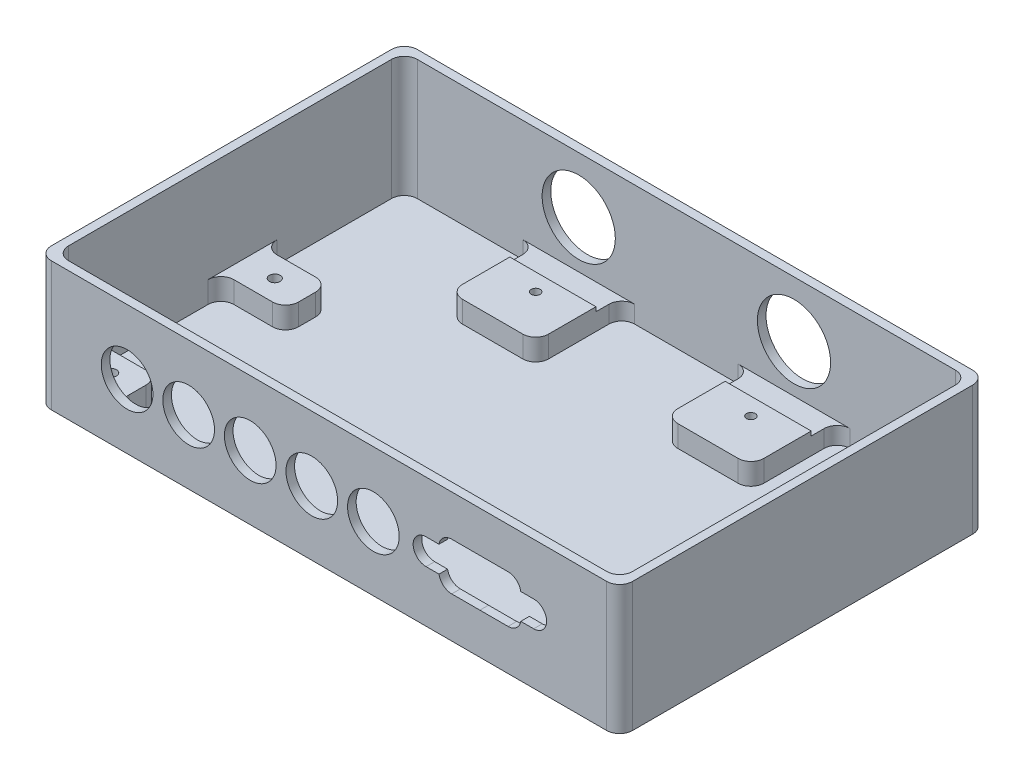
SolidWorks part; units mm, degrees
ref_plane "Ebene vorne" through (0, 0, 0) normal (0, 0, 1) x (1, 0, 0)
ref_plane "Ebene oben" through (0, 0, 0) normal (0, 1, 0) x (1, 0, 0)
ref_plane "Ebene rechts" through (0, 0, 0) normal (1, 0, 0) x (0, 0, -1)
sketch "Skizze1" plane through (0, 0, 0) normal (0, 1, 0) x (1, 0, 0)
  line L1 (0, 0) -> (135, 0)
  line L2 (0, 0) -> (0, 85)
  line L3 (0, 85) -> (135, 85)
  line L4 (135, 0) -> (135, 85)
  dimension "D1" = 85
  dimension "D2" = 135
extrude "Aufsatz-Linear austragen1" add sketch "Skizze1" along normal blind 30
shell "Schale1" thickness 2 removed face at (67.5, 30, -42.5)
sketch "Skizze2" plane through (0, 0, 0) normal (0, 0, 1) x (1, 0, 0)
  line L0 (4.8493, 14.94) -> (121.4088, 14.94) construction
  line L1 (0, 0) -> (135, 0) construction
  line L2 (0, 30) -> (0, 0) construction
  circle A0 centre (20.6, 14.94) radius 6
  circle A1 centre (34.9, 14.94) radius 6
  circle A2 centre (49.2, 14.94) radius 6
  circle A3 centre (63.5, 14.94) radius 6
  circle A4 centre (77.8, 14.94) radius 6
  dimension "D2" = 12
  dimension "D3" = 20.6
  dimension "D4" = 34.9
  dimension "D5" = 49.2
  dimension "D6" = 63.5
  dimension "D7" = 77.8
  dimension "D8" = 12
  dimension "D9" = 12
  dimension "D10" = 12
  dimension "D11" = 12
  dimension "D1" = 14.94
extrude "Schnitt-Linear austragen1" cut sketch "Skizze2" against normal blind 30
sketch "Skizze3" plane through (0, 0, 0) normal (0, 0, 1) x (1, 0, 0)
  line L0 (102.5402, 20.49) -> (95.9981, 20.49)
  line L1 (93.0401, 17.99) -> (90.04, 17.99)
  line L2 (0, 30) -> (0, 0) construction
  line L3 (87.04, 14.99) -> (134.747, 14.99) construction
  line L5 (102.5399, 10.9127) -> (102.5402, 20.49) construction
  line L7 (102.5402, 9.49) -> (95.9981, 9.49)
  line L8 (93.0401, 11.99) -> (90.04, 11.99)
  line L9 (102.5395, 9.49) -> (109.0816, 9.4896)
  line L10 (102.5402, 20.49) -> (109.0822, 20.4896)
  line L11 (112.0398, 11.9895) -> (115.0398, 11.9893)
  line L12 (112.0401, 17.9895) -> (115.0402, 17.9893)
  arc A0 (95.9981, 20.49) -> (93.0401, 17.99) centre (95.9981, 17.49) ccw
  arc A1 (90.04, 17.99) -> (90.04, 11.99) centre (90.04, 14.99) ccw
  arc A2 (95.9981, 9.49) -> (93.0401, 11.99) centre (95.9981, 12.49) cw
  arc A3 (109.0816, 9.4896) -> (112.0398, 11.9895) centre (109.0817, 12.4896) ccw
  arc A4 (115.0402, 17.9893) -> (115.0398, 11.9893) centre (115.04, 14.9893) cw
  arc A5 (109.0822, 20.4896) -> (112.0401, 17.9895) centre (109.082, 17.4896) cw
  point P12 (87.04, 14.99)
  dimension "D7" = 3
  dimension "D1" = 5.5
  dimension "D2" = 9.5
  dimension "D3" = 3
  dimension "D4" = 14.99
  dimension "D5" = 87.04
  dimension "D6" = 15.5
extrude "Schnitt-Linear austragen2" cut sketch "Skizze3" against normal blind 10 contours A5 L10 L0 A0 L1 A1 L8 A2 L7 L9 A3 L11 A4 L12 region at (102.54, 14.9898, 0)
fillet "Verrundung1" radius 3 8 edges at (0, 15, -85) (135, 15, -85) (135, 15, 0) (0, 15, 0) (133, 16, -2) (133, 16, -83) (2, 16, -83) (2, 16, -2)
sketch "Skizze4" plane through (0, 2, 0) normal (0, 1, 0) x (1, 0, 0)
  line L0 (2, 12) -> (13, 12)
  line L1 (2, 80) -> (2, 5) construction
  line L2 (16, 9) -> (16, 2)
  line L3 (5, 2) -> (130, 2) construction
  line L5 (5, 2) -> (16, 2)
  line L6 (2, 12) -> (2, 5)
  line L7 (67.5, 0) -> (67.5, 20.7722) construction
  line L8 (3, 0) -> (132, 0) construction
  line L9 (133, 12) -> (133, 5)
  line L10 (130, 2) -> (119, 2)
  line L11 (119, 9) -> (119, 2)
  line L12 (133, 12) -> (122, 12)
  arc A1 (13, 12) -> (16, 9) centre (13, 9) cw
  arc A2 (2, 5) -> (5, 2) centre (5, 5) ccw construction
  arc A3 (2, 5) -> (5, 2) centre (5, 5) ccw
  arc A4 (133, 5) -> (130, 2) centre (130, 5) cw
  arc A5 (122, 12) -> (119, 9) centre (122, 9) ccw
  point P13 (16, 12)
  line M4 (5, 2) -> (130, 2)
  arc M5 (130, 2) -> (133, 5) centre (130, 5) ccw
  line M6 (133, 5) -> (133, 80)
  line M10 (2, 80) -> (2, 5)
  arc M11 (2, 5) -> (5, 2) centre (5, 5) ccw
  dimension "D5" = 3
  dimension "D3" = 14
  dimension "D4" = 10
extrude "Aufsatz-Linear austragen2" add sketch "Skizze4" along normal blind 5 contours A1 L0 L2 M10 M11 M4 | L12 A5 L11 M4 M5 M6 region at (126, 2, -7) region at (9, 2, -7)
fillet "Verrundung2" radius 3 4 edges at (133, 4.5, -12) (119, 4.5, -2) (16, 4.5, -2) (2, 4.5, -12)
sketch "Skizze5" plane through (0, 2, 0) normal (0, 1, 0) x (1, 0, 0)
  line L0 (2, 80) -> (2, 5) construction
  line L1 (2, 50.4) -> (17, 50.4)
  line L2 (2, 50.4) -> (2, 40.4)
  line L3 (2, 40.4) -> (17, 40.4)
  line L4 (17, 50.4) -> (17, 40.4)
  line L5 (16, 7) -> (7.9271, 7) construction
  line L6 (16, 9) -> (16, 5) construction
  line L7 (17, 45.4) -> (7.9271, 45.4) construction
  line L8 (67.5, 0) -> (67.5, 60.7015) construction
  line L9 (3, 0) -> (132, 0) construction
  line L10 (118, 50.4) -> (118, 40.4)
  line L11 (133, 40.4) -> (118, 40.4)
  line L12 (133, 50.4) -> (133, 40.4)
  line L13 (133, 50.4) -> (118, 50.4)
  dimension "D1" = 38.4
  dimension "D2" = 10
  dimension "D3" = 15
extrude "Aufsatz-Linear austragen3" add sketch "Skizze5" along normal blind 5
fillet "Verrundung3" radius 3 8 edges at (133, 4.5, -40.4) (133, 4.5, -50.4) (118, 4.5, -40.4) (118, 4.5, -50.4) (2, 4.5, -50.4) (17, 4.5, -50.4) (17, 4.5, -40.4) (2, 4.5, -40.4)
sketch "Skizze6" plane through (0, 0, -85) normal (0, 0, -1) x (-1, 0, 0)
  line L0 (-128.5127, 17) -> (-8.2871, 17) construction
  line L1 (-132, 0) -> (-3, 0) construction
  line L2 (-67.5, 0) -> (-67.5, 33.8667) construction
  circle A0 centre (-92.5, 17) radius 8.5
  circle A1 centre (-42.5, 17) radius 8.5
  dimension "D2" = 17
  dimension "D3" = 50
  dimension "D1" = 17
extrude "Schnitt-Linear austragen3" cut sketch "Skizze6" against normal blind 5
sketch "Skizze7" plane through (0, 2, 0) normal (0, 1, 0) x (1, 0, 0)
  line L0 (67.5, 85) -> (67.5, 35.1088) construction
  line L1 (132, 85) -> (3, 85) construction
  line L2 (130, 83) -> (5, 83) construction
  line L3 (32.5, 63) -> (52.5, 63)
  line L4 (32.5, 63) -> (32.5, 83)
  line L5 (32.5, 83) -> (52.5, 83)
  line L6 (52.5, 63) -> (52.5, 83)
  line L7 (42.5, 63) -> (42.5, 71.5986) construction
  line L8 (0, 82) -> (0, 3) construction
  line L9 (32.5, 63) -> (32.5, 83)
  line L10 (52.5, 63) -> (52.5, 83)
  line L11 (102.5, 83) -> (82.5, 83)
  line L12 (82.5, 63) -> (82.5, 83)
  line L13 (102.5, 63) -> (82.5, 63)
  line L14 (102.5, 63) -> (102.5, 83)
  line M17 (130, 83) -> (5, 83)
  dimension "D1" = 42.5
  dimension "D2" = 20
  dimension "D3" = 20
extrude "Aufsatz-Linear austragen4" add sketch "Skizze7" along normal blind 5 contours L3 L6 L4 M17 | L13 L14 L12 M17 region at (42.5, 2, -73) region at (92.5, 2, -73)
fillet "Verrundung4" radius 3 8 edges at (102.5, 4.5, -83) (102.5, 4.5, -63) (82.5, 4.5, -63) (82.5, 4.5, -83) (32.5, 4.5, -83) (32.5, 4.5, -63) (52.5, 4.5, -83) (52.5, 4.5, -63)
hole_wizard "M3 Gewindebohrung1" positions "Skizze8" profile "Skizze9" tap size "M3" standard "DIN"
sketch "Skizze8" plane through (0, 7, 0) normal (0, 1, 0) x (1, 0, 0)
  line L1 (125.5, 7.4) -> (9.5, 7.4) construction
  line L2 (125.5, 7.4) -> (125.5, 45.4) construction
  line L3 (125.5, 45.4) -> (9.5, 45.4) construction
  line L4 (9.5, 7.4) -> (9.5, 45.4) construction
  line L5 (19, 2) -> (116, 2) construction
  line L6 (133, 15) -> (133, 37.4) construction
  line L7 (67.5, 0) -> (67.5, 59.3993) construction
  line L8 (3, 0) -> (132, 0) construction
  point P1 (125.5, 7.4)
  point P2 (9.5, 45.4)
  point P117 (125.5, 45.4)
  point P118 (9.5, 7.4)
  dimension "D1" = 5.4
  dimension "D2" = 7.5
  dimension "D3" = 38
  dimension "D4" = 116
sketch "Skizze9" plane through (125.5, 7, -7.4) normal (1, 0, 0) x (0, 0, 1)
  line L0 (0, 0) -> (0, 9.2511)
  line L1 (0, 9.2511) -> (1.25, 8.5)
  line L2 (1.25, 8.5) -> (1.25, 0)
  line L5 (1.25, 0) -> (0, 0)
  line L10 (0, 9.2511) -> (-1.25, 8.5) construction
  line L11 (0, -6.35) -> (0, 107.95) construction
  dimension "Bohrerdurchmesser" = 2.5
  dimension "Bohrungstiefe" = 8.5
  dimension "Spitzenwinkel" = 118
cosmetic thread "Bohrungsgewinde1" parameters "D1"=6, "D2"=3
cosmetic thread "Bohrungsgewinde2" parameters "D1"=6, "D2"=3
cosmetic thread "Bohrungsgewinde3" parameters "D1"=6, "D2"=3
cosmetic thread "Bohrungsgewinde4" parameters "D1"=6, "D2"=3
hole_wizard "M2.5 Gewindebohrung1" positions "Skizze10" profile "Skizze11" tap size "M2.5" standard "DIN"
sketch "Skizze10" plane through (0, 7, 0) normal (0, 1, 0) x (1, 0, 0)
  line L0 (92.5, 63) -> (92.5, 83) construction
  line L1 (99.5, 63) -> (85.5, 63) construction
  line L2 (42.5, 63) -> (42.5, 83) construction
  line L3 (35.5, 63) -> (49.5, 63) construction
  line L4 (105.5, 83) -> (79.5, 83) construction
  point P10 (92.5, 73)
  point P12 (42.5, 73)
  point P17 (0, 0)
  dimension "D1" = 10
sketch "Skizze11" plane through (42.5, 7, -73) normal (1, 0, 0) x (0, 0, 1)
  line L0 (0, 0) -> (0, 7.8659)
  line L1 (0, 7.8659) -> (1.025, 7.25)
  line L2 (1.025, 7.25) -> (1.025, 0)
  line L5 (1.025, 0) -> (0, 0)
  line L10 (0, 7.8659) -> (-1.025, 7.25) construction
  line L11 (0, -6.35) -> (0, 107.95) construction
  dimension "Bohrerdurchmesser" = 2.05
  dimension "Bohrungstiefe" = 7.25
  dimension "Spitzenwinkel" = 118
cosmetic thread "Bohrungsgewinde5" parameters "D1"=5, "D2"=2.5
cosmetic thread "Bohrungsgewinde6" parameters "D1"=5, "D2"=2.5
sketch "Skizze12" plane through (0, 7, 0) normal (0, 1, 0) x (1, 0, 0)
  line L0 (130, 83) -> (105.5, 83) construction
  line L1 (108.8489, 83) -> (23.8489, 83)
  line L2 (108.8489, 83) -> (108.8489, 77)
  line L3 (108.8489, 77) -> (23.8489, 77)
  line L4 (23.8489, 83) -> (23.8489, 77)
  dimension "D1" = 6
  dimension "D2" = 85
extrude "Schnitt-Linear austragen4" cut sketch "Skizze12" against normal blind 1
